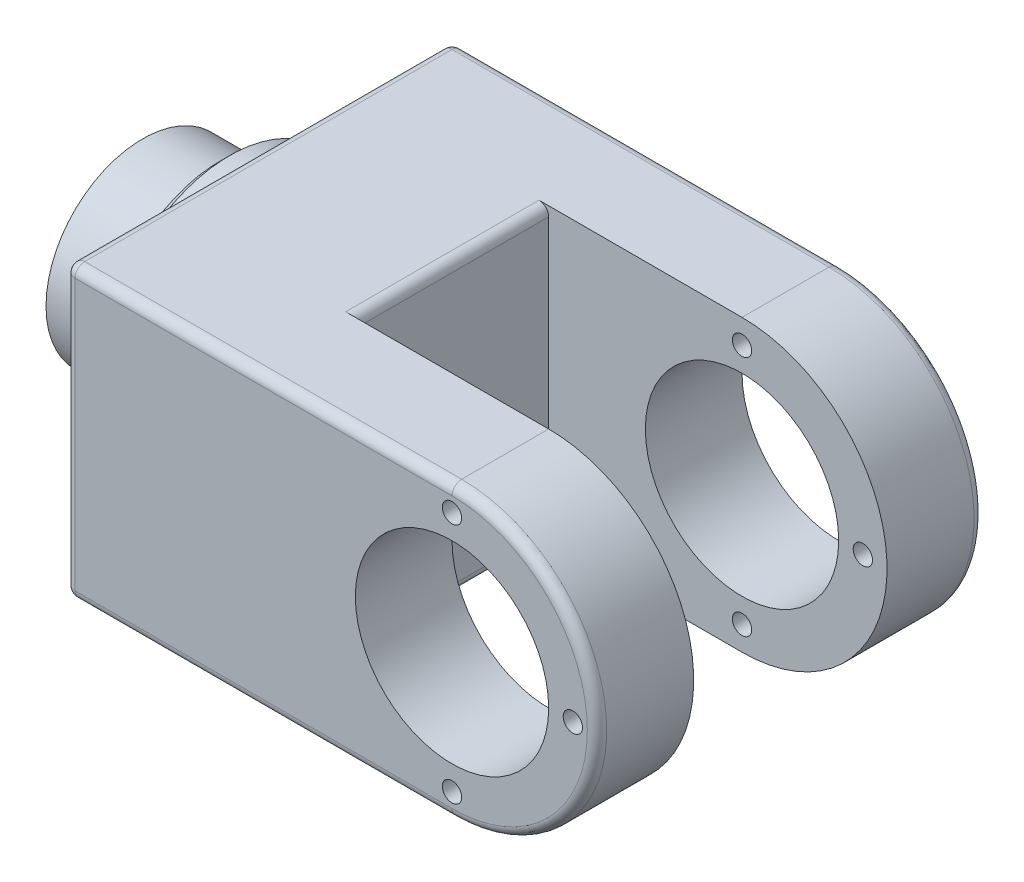
SolidWorks part; units mm, degrees
material "Alloy Steel"
ref_plane "Front" through (0, 0, 0) normal (0, 0, 1) x (1, 0, 0)
ref_plane "Top" through (0, 0, 0) normal (0, 1, 0) x (1, 0, 0)
ref_plane "Right" through (0, 0, 0) normal (1, 0, 0) x (0, 0, -1)
sketch "Sketch1" plane through (0, 0, 0) normal (0, 0, 1) x (1, 0, 0)
  line L0 (0, 75) -> (-200, 75)
  line L1 (-200, 75) -> (-200, -75)
  line L2 (-200, -75) -> (0, -75)
  arc A0 (0, -75) -> (0, 75) centre (0, 0) ccw
  dimension "D1" = 150
  dimension "D2" = 200
extrude "Boss-Extrude1" add sketch "Sketch1" along normal mid plane 200
sketch "Sketch2" plane through (0, 0, 0) normal (0, 0, 1) x (1, 0, 0)
  line L0 (0, 75) -> (-100, 75)
  line L1 (0, 75) -> (-200, 75) construction
  line L2 (-100, 75) -> (-100, -75)
  line L3 (-200, -75) -> (0, -75) construction
  line L4 (-100, -75) -> (0, -75)
  arc A0 (0, -75) -> (0, 75) centre (0, 0) ccw construction
  arc A1 (0, -75) -> (0, 75) centre (0, 0) ccw
  dimension "D1" = 100
extrude "Cut-Extrude1" cut sketch "Sketch2" against normal mid plane 100
sketch "Sketch3" plane through (-200, 0, 0) normal (-1, 0, 0) x (0, 0, 1)
  circle A0 centre (0, 0) radius 65
  dimension "D1" = 130
extrude "Boss-Extrude2" add sketch "Sketch3" along normal blind 20
sketch "Sketch4" plane through (-220, 0, 0) normal (-1, 0, 0) x (0, 0, 1)
  circle A0 centre (0, 0) radius 50
  dimension "D1" = 100
extrude "Boss-Extrude3" add sketch "Sketch4" along normal blind 40
chamfer "Chamfer1" distance 5 angle 45 1 edges at (-220, 0, 65)
sketch "Sketch5" plane through (0, 0, 100) normal (0, 0, 1) x (1, 0, 0)
  circle A0 centre (0, 0) radius 62.5
  circle A1 centre (0, 62.5) radius 5
  circle A2 centre (62.5, 0) radius 5
  circle A3 centre (0, -62.5) radius 5
  point P11 (0, 0)
  dimension "D1" = 125
  dimension "D2" = 10
  dimension "D3" = 3
extrude "Cut-Extrude2" cut sketch "Sketch5" against normal through all contours A1 | A2 | A3
fillet "Fillet1" radius 5 14 edges at (-100, -75, -100) (75, 0, -100) (-100, -75, 100) (75, 0, 100) (-220, 0, 50) (-200, 0, -65) (-200, -75, 0) (-200, 75, 0) (-200, 0, -100) (-200, 0, 100) (-100, -75, 0) (-100, 75, 0) (-100, 75, -100) (-100, 75, 100)
sketch "Sketch6" plane through (0, 0, 100) normal (0, 0, 1) x (1, 0, 0)
  circle A0 centre (0, 0) radius 50
  dimension "D1" = 100
extrude "Cut-Extrude3" cut sketch "Sketch6" against normal through all
